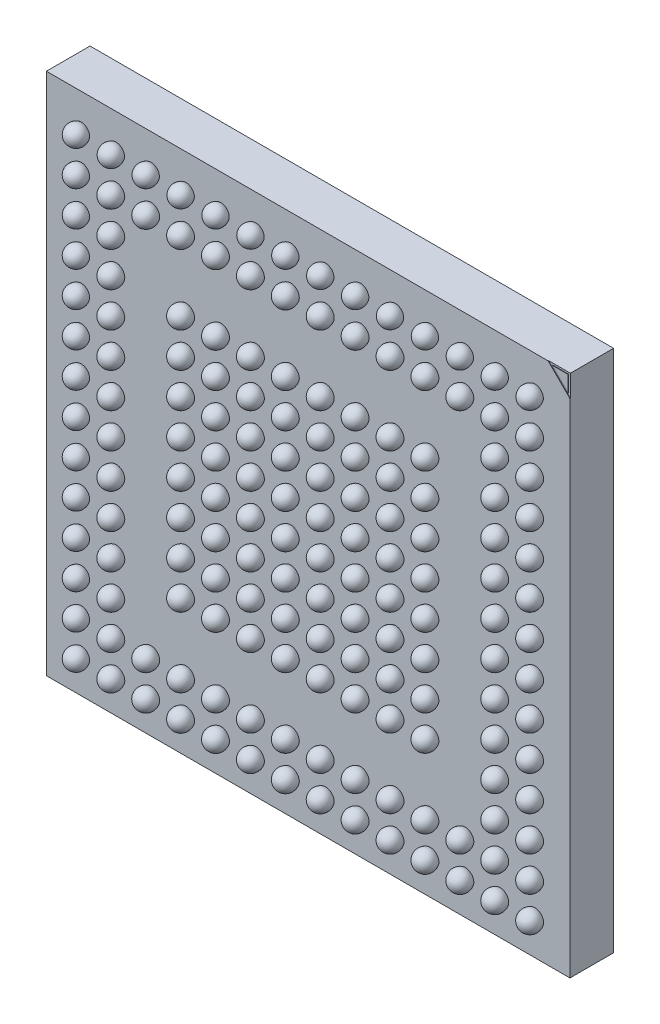
SolidWorks part; units mm, degrees
ref_plane "Front Plane" through (0, 0, 0) normal (0, 0, 1) x (1, 0, 0)
ref_plane "Top Plane" through (0, 0, 0) normal (0, 1, 0) x (1, 0, 0)
ref_plane "Right Plane" through (0, 0, 0) normal (1, 0, 0) x (0, 0, -1)
sketch "Sketch1" plane through (0, 0, 0) normal (0, 0, 1) x (1, 0, 0)
  line L1 (-6, 6) -> (6, 6)
  line L2 (-6, 6) -> (-6, -6)
  line L3 (-6, -6) -> (6, -6)
  line L4 (6, 6) -> (6, -6)
  line L5 (-6, 6) -> (6, -6) construction
  line L6 (-6, -6) -> (6, 6) construction
  point P0 (0, 0)
  dimension "D1" = 12
  dimension "D2" = 12
extrude "Boss-Extrude1" add sketch "Sketch1" along normal blind 1
sketch3d "3DSketch2" plane through (0, 0, 0) normal (0, 0, 1) x (1, 0, 0)
  dimension "D1" = 0.12
sketch3d "3DSketch1" plane through (0, 0, 0) normal (0, 0, 1) x (1, 0, 0)
  dimension "D1" = 0.01
sketch "Sketch3" plane through (0, 0, 1.12) normal (0, 0, 1) x (1, 0, 0)
  line L0 (-5.2, 5.425) -> (-5.2, 4.975)
  arc A0 (-5.2, 5.425) -> (-5.2, 4.975) centre (-5.2, 5.2) ccw
  dimension "D2" = 0.225
  dimension "D1" = 5.2
  dimension "D3" = 5.2
revolve "Revolve1" add sketch "Sketch3" angle 360 about L0
pattern_linear "LPattern1" count 14 spacing 0.8 along (1, 0, 0) of "Revolve1"
pattern_linear "LPattern2" count 14 spacing 0.8 along (0, -1, 0) of "Revolve1"
sketch "Sketch4" plane through (0, 0, 1) normal (0, 0, 1) x (1, 0, 0)
  line L0 (-6, -6) -> (6, 6) construction
sketch "Sketch5" plane through (0, 0, 1.12) normal (0, 0, 1) x (1, 0, 0)
  line L0 (5.2, 5.2) -> (5.2, -5.2) construction
  line L1 (-6, -6) -> (6, 6) construction
  line L2 (5.2, 4.63) -> (5.2, 4.17)
  arc A0 (5.2, 4.63) -> (5.2, 4.17) centre (5.2, 4.4) ccw
  dimension "D2" = 0.23
  dimension "D1" = 0.8
revolve "Revolve2" add sketch "Sketch5" angle 360 about L0
pattern_linear "LPattern3" count 12 spacing 0.8 along (0, -1, 0) of "Revolve2"
sketch "Sketch8" plane through (0, 0, 1.12) normal (0, 0, 1) x (1, 0, 0)
  line L0 (5.2, -4.9726) -> (5.2, -5.4326)
  line L1 (-5.2026, -5.2026) -> (6.4563, -5.2026) construction
  line L2 (-6, -6) -> (6, 6) construction
  line L3 (5.2, 5.2) -> (5.2, -5.8448) construction
  arc A0 (5.2, -4.9726) -> (5.2, -5.4326) centre (5.2, -5.2026) cw
  dimension "D2" = 0.23
  dimension "D1" = 0
  dimension "D3" = 0
revolve "Revolve3" add sketch "Sketch8" angle 360 about L0
pattern_linear "LPattern4" count 13 spacing 0.8 along (-1, 0, 0) of "Revolve3"
sketch "Sketch9" plane through (0, 0, 1.12) normal (0, 0, 1) x (1, 0, 0)
  line L0 (-5.2, 4.4) -> (-4.4, 4.4) construction
  line L1 (-4.4, 4.4) -> (-4.4, 5.2) construction
  line L2 (-4.4, 4.63) -> (-4.4, 4.17)
  arc A0 (-4.4, 4.63) -> (-4.4, 4.17) centre (-4.4, 4.4) cw
  dimension "D1" = 0.23
revolve "Revolve4" add sketch "Sketch9" angle 360 about L2
pattern_linear "LPattern5" count 12 spacing 0.8 along (1, 0, 0) of "Revolve4"
mirror "Mirror3" about plane through (0, 0, 0) normal (0, 1, 0) of "LPattern5", "Revolve4"
pattern_linear "LPattern6" count 11 spacing 0.8 along (0, -1, 0) of "Revolve4"
mirror "Mirror4" about plane through (0, 0, 0) normal (1, 0, 0) of "LPattern6"
sketch "Sketch10" plane through (0, 0, 1.12) normal (0, 0, 1) x (1, 0, 0)
  line L0 (-2.8, 4.4) -> (-2.8, 2.8) construction
  line L1 (-2.8, 2.8) -> (-4.4, 2.8) construction
  line L2 (-2.8, 3.03) -> (-2.8, 2.57)
  arc A0 (-2.8, 3.03) -> (-2.8, 2.57) centre (-2.8, 2.8) ccw
  dimension "D1" = 0.23
revolve "Revolve5" add sketch "Sketch10" angle 360 about L2
pattern_linear "LPattern7" count 8 spacing 0.8 along (1, 0, 0) count 8 spacing 0.8 along (0, -1, 0) of "Revolve5"
sketch "Sketch11" plane through (0, 0, 0) normal (0, 0, -1) x (-1, 0, 0)
  line L0 (70.5838, 258.2384) -> (518.5838, 258.2384) construction
  line L1 (-4.3839, 0.8798) -> (-4.3839, 4.3103)
  line L2 (-4.3839, 4.3103) -> (-3.2934, 4.3103)
  line L3 (-3.2934, 4.3103) -> (-1.6992, 2.5075)
  line L4 (-1.6992, 2.5075) -> (-1.6992, 4.3103)
  line L5 (-1.6992, 4.3103) -> (-0.3405, 4.3103)
  line L6 (-0.3405, 4.3103) -> (0.2837, 3.3039)
  line L7 (0.2837, 3.3039) -> (0.9053, 4.3103)
  line L8 (0.9053, 4.3103) -> (3.9962, 4.3103)
  line L9 (4.5962, 3.7103) -> (4.5962, 2.7781)
  line L10 (3.9962, 2.1781) -> (2.3289, 2.1781)
  line L11 (2.3289, 2.1781) -> (2.3289, 0.8446)
  line L12 (2.3289, 0.8446) -> (0.9053, 0.8446)
  line L13 (0.9053, 0.8446) -> (0.2837, 1.8467)
  line L14 (0.2837, 1.8467) -> (-0.3243, 0.8623)
  line L15 (-0.3243, 0.8623) -> (-1.5859, 0.8623)
  line L16 (-1.5859, 0.8623) -> (-3.2198, 2.71)
  line L17 (-3.2198, 2.71) -> (-3.2198, 0.8798)
  line L18 (-3.2198, 0.8798) -> (-4.3839, 0.8798)
  line L19 (-4.2197, 1.0451) -> (-4.2197, 4.1148)
  line L20 (-4.2197, 4.1148) -> (-3.3227, 4.1148)
  line L21 (-3.3227, 4.1148) -> (-1.4957, 1.9924)
  line L22 (-1.4957, 1.9924) -> (-1.4957, 3.9002)
  line L23 (-1.4957, 3.9002) -> (-0.6806, 2.5941)
  line L24 (-0.6806, 2.5941) -> (-1.5943, 1.0735)
  line L25 (-1.5943, 1.0735) -> (-3.3751, 3.1423)
  line L26 (-3.3751, 3.1423) -> (-3.3751, 1.0451)
  line L27 (-3.3751, 1.0451) -> (-4.2197, 1.0451)
  line L28 (-1.4452, 4.1504) -> (-0.4308, 4.1504)
  line L29 (-0.4308, 4.1504) -> (0.2945, 2.9894)
  line L30 (0.2945, 2.9894) -> (0.9906, 4.1504)
  line L31 (0.9906, 4.1504) -> (2.0032, 4.1504)
  line L32 (2.0032, 4.1504) -> (1.0604, 2.5778)
  line L33 (1.0604, 2.5778) -> (2.0353, 1.0173)
  line L34 (2.0353, 1.0173) -> (1.0294, 1.0173)
  line L35 (1.0294, 1.0173) -> (0.2945, 2.1936)
  line L36 (0.2945, 2.1936) -> (-0.4046, 1.0274)
  line L37 (-0.4046, 1.0274) -> (-1.4452, 1.0274)
  line L38 (-1.4452, 1.0274) -> (-0.4588, 2.5941)
  line L39 (-0.4588, 2.5941) -> (-1.4452, 4.1504)
  line L40 (2.2198, 4.1504) -> (3.8592, 4.1274)
  line L41 (4.4508, 3.519) -> (4.4422, 2.907)
  line L42 (3.8422, 2.3154) -> (2.1526, 2.3154)
  line L43 (2.1526, 2.3154) -> (2.1526, 1.1096)
  line L44 (2.1526, 1.1096) -> (1.2674, 2.5778)
  line L45 (1.2674, 2.5778) -> (2.2198, 4.1504)
  line L46 (2.1526, 3.694) -> (3.7071, 3.694)
  line L47 (3.9071, 3.494) -> (3.9071, 2.9781)
  line L48 (3.7071, 2.7781) -> (2.1526, 2.7781)
  line L49 (2.1526, 3.694) -> (2.1526, 2.7781)
  line L50 (2.3133, 3.528) -> (3.5202, 3.528)
  line L51 (2.3133, 3.528) -> (2.3133, 2.9549)
  line L52 (2.3133, 2.9549) -> (3.5202, 2.9549)
  line L53 (3.7202, 3.328) -> (3.7202, 3.1549)
  arc A0 (4.5962, 2.7781) -> (3.9962, 2.1781) centre (3.9962, 2.7781) cw
  arc A1 (3.9962, 4.3103) -> (4.5962, 3.7103) centre (3.9962, 3.7103) cw
  arc A2 (4.4422, 2.907) -> (3.8422, 2.3154) centre (3.8422, 2.9154) cw
  arc A3 (3.8592, 4.1274) -> (4.4508, 3.519) centre (3.8508, 3.5274) cw
  arc A4 (3.5202, 2.9549) -> (3.7202, 3.1549) centre (3.5202, 3.1549) ccw
  arc A5 (3.5202, 3.528) -> (3.7202, 3.328) centre (3.5202, 3.328) cw
  arc A6 (3.9071, 2.9781) -> (3.7071, 2.7781) centre (3.7071, 2.9781) cw
  arc A7 (3.7071, 3.694) -> (3.9071, 3.494) centre (3.7071, 3.494) cw
extrude "Boss-Extrude2" add sketch "Sketch11" along normal blind 0.01 contours A1 L8 L7 L6 L5 L4 L3 L2 L1 L18 L17 L16 L15 L14 L13 L12 L11 L10 A0 L9 L38 L39 L28 L29 L30 L31 L32 L33 L34 L35 L36 L37 L26 L27 L19 L20 L21 L22 L23 L24 L25 L40 A3 L41 A2 L42 L43 L44 | A7 L46 L49 L48 A6 L47 L50 A5 L53 A4 L52 L51 region at (4.2876, 2.595, 0) region at (-2.9298, 3.6742, 0)
sketch "Sketch12" plane through (0, 0, 0) normal (0, 0, -1) x (-1, 0, 0)
  line L0 (-3.1438, -4.3314) -> (4.1393, -4.3314) construction
  text T0 "<b>SJA1105</b>" font "Century Gothic" height 1.2
extrude "Boss-Extrude3" add sketch "Sketch12" along normal blind 0.01
sketch "Sketch13" plane through (0, 0, 1) normal (0, 0, 1) x (1, 0, 0)
  line L0 (6, 6) -> (6, 5.5)
  line L1 (6, -6) -> (6, 6) construction
  line L2 (6, 5.5) -> (5.5, 6)
  line L3 (6, 6) -> (-6, 6) construction
  line L4 (5.5, 6) -> (6, 6)
  dimension "D1" = 0.5
  dimension "D2" = 0.5
extrude "Cut-Extrude1" cut sketch "Sketch13" against normal blind 0.01
sketch "Sketch14" plane through (0, 0, 0.99) normal (0, 0, 1) x (1, 0, 0)
  line L0 (5.5966, 5.96) -> (5.96, 5.96)
  line L1 (5.96, 5.96) -> (5.96, 5.5966)
  line L2 (5.96, 5.5966) -> (5.5966, 5.96)
  line L3 (6, 5.5) -> (6, 6) construction
  line L4 (6, 6) -> (5.5, 6) construction
  line L5 (5.5, 6) -> (6, 5.5) construction
  dimension "D1" = 0.04
  dimension "D2" = 0.04
  dimension "D3" = 0.04
  dimension "D4" = 0.04
extrude "Boss-Extrude4" add sketch "Sketch14" along normal up to surface (0.01 mm away) up to face at (1.1, 1.1, 1)
